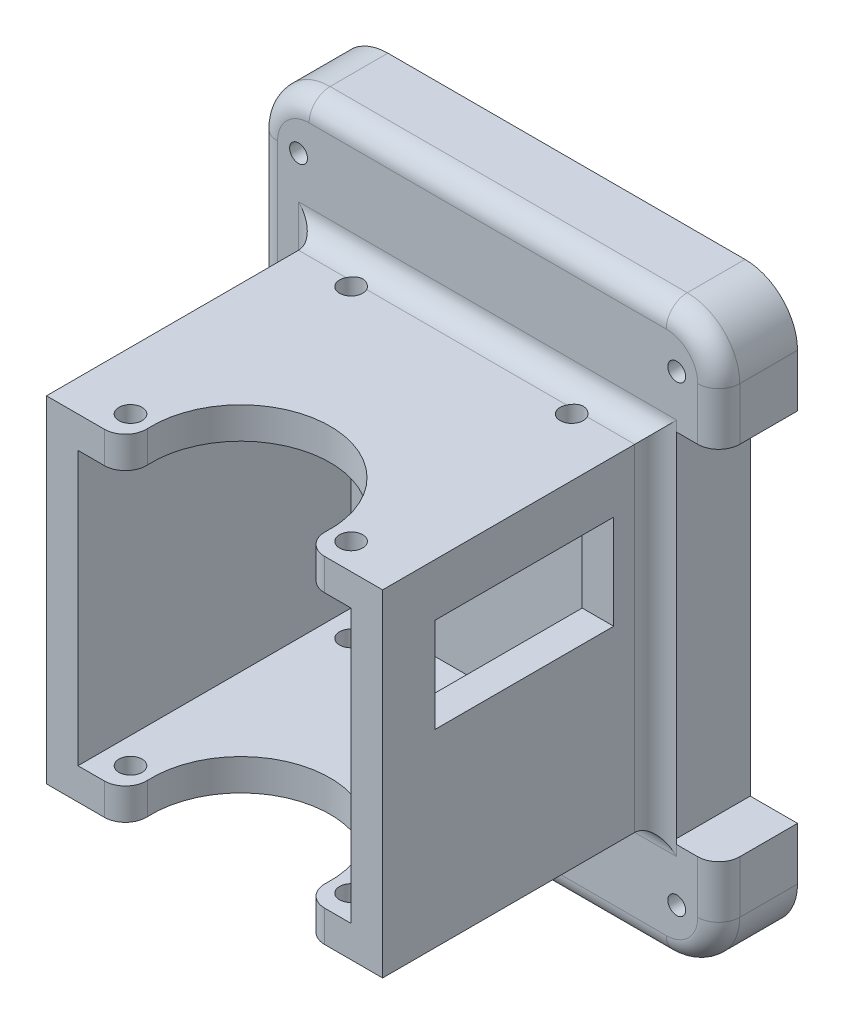
SolidWorks part; units mm, degrees
material "ABS"
ref_plane "正面" through (0, 0, 0) normal (0, 0, 1) x (1, 0, 0)
ref_plane "平面" through (0, 0, 0) normal (0, 1, 0) x (1, 0, 0)
ref_plane "右側面" through (0, 0, 0) normal (1, 0, 0) x (0, 0, -1)
sketch "ｽｹｯﾁ2" plane through (0, 0, 0) normal (0, 0, 1) x (1, 0, 0)
  line L0 (19.8, 0) -> (-19.8, 0) construction
  line L1 (-16, 0) -> (16, 0)
  line L2 (-16, 0) -> (-16, 32)
  line L3 (-16, 32) -> (16, 32)
  line L4 (16, 0) -> (16, 32)
  line L5 (-13, 3) -> (13, 3)
  line L6 (13, 3) -> (13, 29)
  line L7 (-13, 29) -> (13, 29)
  line L8 (-13, 3) -> (-13, 29)
  dimension "D1" = 32
  dimension "D2" = 32
  dimension "D3" = 3
extrude "ﾎﾞｽ - 押し出し1" add sketch "ｽｹｯﾁ2" along normal blind 26
sketch "ｽｹｯﾁ3" plane through (0, 0, 0) normal (0, 0, -1) x (-1, 0, 0)
  line L5 (-16, 0) -> (-16, 32) construction
  line L6 (-22, 43) -> (22, 43)
  line L7 (-22, 43) -> (-22, -11)
  line L8 (-22, -11) -> (22, -11)
  line L9 (22, 43) -> (22, -11)
  line L10 (16, 32) -> (16, 0) construction
  line L11 (-16, 32) -> (16, 32) construction
  line L12 (14.3, 0) -> (-14.3, 0) construction
  dimension "D1" = 6
  dimension "D2" = 6
  dimension "D3" = 11
  dimension "D4" = 11
extrude "ﾎﾞｽ - 押し出し2" add sketch "ｽｹｯﾁ3" along normal blind 7.5
fillet "ﾌｨﾚｯﾄ1" radius 2 4 edges at (0, 0, 0) (16, 16, 0) (-16, 16, 0) (0, 32, 0)
fillet "ﾌｨﾚｯﾄ2" radius 2 4 edges at (-22, 16, 0) (0, 43, 0) (22, 16, 0) (0, -11, 0)
sketch "ｽｹｯﾁ5" plane through (0, 0, 0) normal (0, -1, 0) x (1, 0, 0)
  line L0 (0, 26) -> (0, 0) construction
  line L1 (-16, 26) -> (16, 26) construction
  line L3 (-10.5, 23.5) -> (10.5, 23.5) construction
  line L4 (-10.5, 23.5) -> (-10.5, 2.5) construction
  line L5 (-10.5, 2.5) -> (10.5, 2.5) construction
  line L6 (10.5, 23.5) -> (10.5, 2.5) construction
  line L7 (-10.5, 23.5) -> (10.5, 2.5) construction
  line L8 (-10.5, 2.5) -> (10.5, 23.5) construction
  circle A0 centre (10.5, 23.5) radius 1.1
  circle A1 centre (-10.5, 23.5) radius 1.1
  circle A2 centre (-10.5, 2.5) radius 1.1
  circle A3 centre (10.5, 2.5) radius 1.1
  circle A4 centre (0, 23.5) radius 8.5
  point P5 (0, 13)
  dimension "D4" = 2.2
  dimension "D5" = 17
  dimension "D1" = 21
  dimension "D2" = 21
  dimension "D3" = 13
extrude "ｶｯﾄ - 押し出し1" cut sketch "ｽｹｯﾁ5" against normal through all both and the other way through all
fillet "ﾌｨﾚｯﾄ3" radius 2 4 edges at (-8.124, 30.5, 26) (8.124, 30.5, 26) (-8.124, 1.5, 26) (8.124, 1.5, 26)
sketch "ｽｹｯﾁ7" plane through (0, 0, -7.5) normal (0, 0, -1) x (-1, 0, 0)
  line L1 (-18, -6) -> (18, -6) construction
  line L2 (-18, -6) -> (-18, 38) construction
  line L3 (-18, 38) -> (18, 38) construction
  line L4 (-22, 43) -> (-22, -11)
  line L5 (-22, -11) -> (22, -11)
  line L6 (22, -11) -> (22, 43)
  line L7 (22, 43) -> (-22, 43)
  line L8 (-22, 43) -> (-22, -11) construction
  line L9 (-22, -11) -> (22, -11) construction
  line L10 (22, -11) -> (22, 43) construction
  line L11 (22, 43) -> (-22, 43) construction
  line L12 (18, -6) -> (18, 38) construction
  circle A0 centre (-18, -6) radius 0.85
  circle A1 centre (-18, 38) radius 0.85
  circle A2 centre (18, 38) radius 0.85
  circle A3 centre (18, -6) radius 0.85
  dimension "D6" = 1.7
  dimension "D2" = 5
  dimension "D3" = 5
  dimension "D4" = 4
  dimension "D5" = 4
  dimension "D1" = 0
extrude "ｶｯﾄ - 押し出し2" cut sketch "ｽｹｯﾁ7" against normal through all
fillet "ﾌｨﾚｯﾄ4" radius 5 8 edges at (-21.4142, 42.4142, -0.5858) (-21.4142, -10.4142, -0.5858) (21.4142, -10.4142, -0.5858) (21.4142, 42.4142, -0.5858) (22, 43, -4.75) (22, -11, -4.75) (-22, -11, -4.75) (-22, 43, -4.75)
sketch "ｽｹｯﾁ9" plane through (16, 0, 0) normal (1, 0, 0) x (0, 0, -1)
  line L0 (-2, 0) -> (-2, 32) construction
  line L1 (-21, 27) -> (-4, 27)
  line L2 (-21, 27) -> (-21, 18)
  line L3 (-21, 18) -> (-4, 18)
  line L4 (-4, 27) -> (-4, 18)
  line L5 (-26, 32) -> (-2, 32) construction
  line L6 (-26, 0) -> (-26, 32) construction
  dimension "D1" = 2
  dimension "D2" = 5
  dimension "D3" = 9
  dimension "D4" = 5
extrude "ｶｯﾄ - 押し出し4" cut sketch "ｽｹｯﾁ9" against normal blind 10
sketch "ｽｹｯﾁ10" plane through (0, 0, 0) normal (0, 0, 1) x (1, 0, 0)
  line L1 (17.5, -1) -> (22, -1)
  line L2 (17.5, -1) -> (17.5, 33)
  line L3 (17.5, 33) -> (22, 33)
  line L4 (22, -1) -> (22, 33)
  line L5 (22, 38) -> (22, -6) construction
  line L6 (17, -11) -> (-17, -11) construction
  line L7 (-17, 43) -> (17, 43) construction
  point P9 (0, 0)
  dimension "D1" = 4.5
  dimension "D2" = 10
  dimension "D3" = 10
extrude "ｶｯﾄ - 押し出し5" cut sketch "ｽｹｯﾁ10" against normal through all
